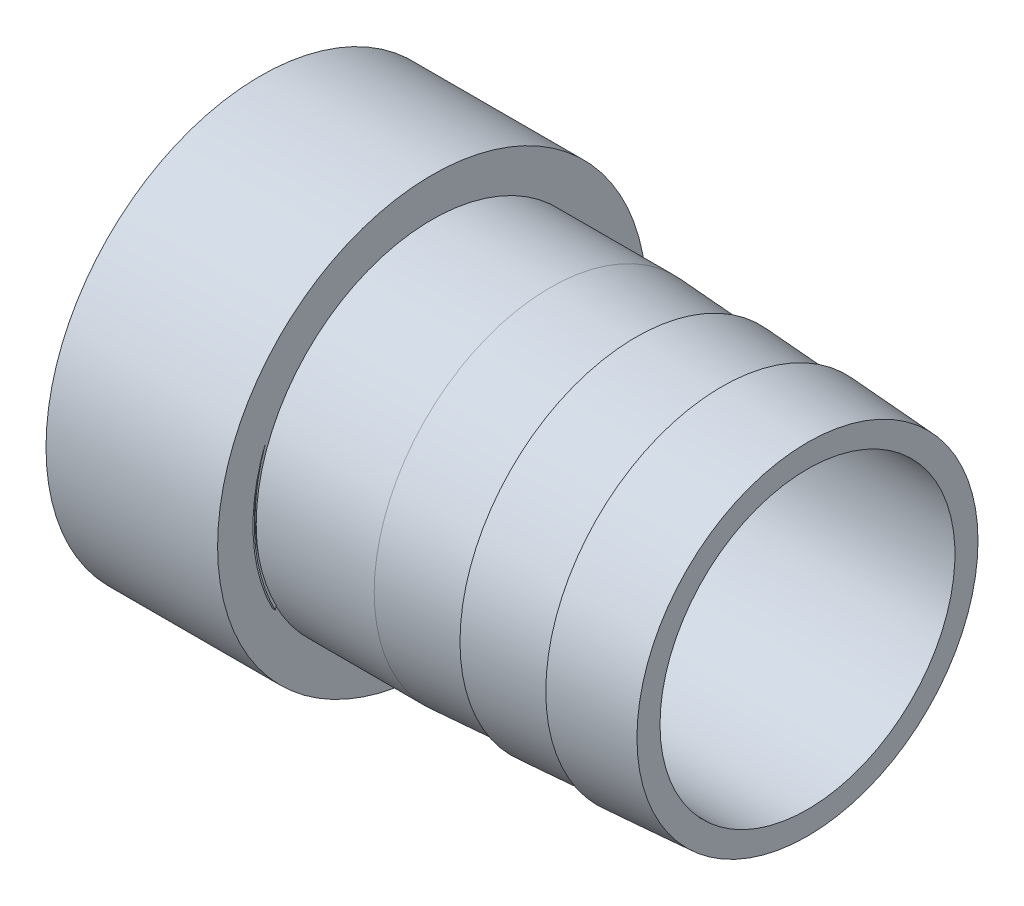
SolidWorks part; units mm, degrees
ref_plane "Płaszczyzna przednia" through (0, 0, 0) normal (0, 0, 1) x (1, 0, 0)
ref_plane "Płaszczyzna górna" through (0, 0, 0) normal (0, 1, 0) x (1, 0, 0)
ref_plane "Płaszczyzna prawa" through (0, 0, 0) normal (1, 0, 0) x (0, 0, -1)
sketch "Szkic1" plane through (0, 0, 0) normal (0, 0, 1) x (1, 0, 0)
  line L0 (0, 0) -> (21.6019, 0) construction
  line L1 (0, 16.4) -> (11, 16.4)
  line L2 (11, 16.4) -> (19, 15.9)
  line L3 (19, 15.9) -> (19, 16.4)
  line L4 (19, 16.4) -> (27, 15.9)
  line L5 (27, 15.9) -> (27, 16.4)
  line L6 (27, 16.4) -> (35, 15.9)
  line L7 (35, 15.9) -> (35, 13.75)
  line L8 (35, 15.9) -> (35, 16.4) [skipped]
  line L9 (35, 13.75) -> (-1.2, 13.75)
  line L10 (-1.2, 13.75) -> (-1.2, 16.7)
  line L11 (-1.2, 16.7) -> (-16, 16.7)
  line L12 (-16, 16.7) -> (-16, 20)
  line L13 (-16, 20) -> (0, 20)
  line L14 (0, 20) -> (0, 16.4)
  dimension "D1" = 11
  dimension "D2" = 16.4
  dimension "D3" = 8
  dimension "D4" = 15.9
  dimension "D6" = 13.75
  dimension "D7" = 14.8
  dimension "D8" = 20
  dimension "D9" = 3.3
  dimension "D10" = 51
  dimension "D5" = 3
revolve "Obrót1" add sketch "Szkic1" angle 360 about L0
thread "Gwint1" pitch 1.9538 method extrude profile "Profil gwintu1" start angle 0, offset 0, length 0, pitch 1.9538, diameter 33.4
ref_plane "Płaszczyzna1" through (-16, 0, -16.7) normal (0, 1, 0) x (0, 0, 1)
sketch "Profil gwintu1" plane through (-16, 0, -16.7) normal (0, 1, 0) x (0, 0, 1)
  line L0 (0, 0) -> (0, 1.9538) construction
  line L1 (0, 0) -> (1.0576, 0.6106)
  line L2 (1.0576, 0.6106) -> (1.0576, 0.8548)
  line L3 (1.0576, 0.8548) -> (0, 1.4654)
  line L4 (1.0576, 0.7327) -> (0, 0.7327) construction
  line L11 (0, 0) -> (0, 1.4654)
  point P2 (0, 0)
  dimension "Pitch" = 1.9538
  dimension "Profile_Angle" = 60
  dimension "Profile_Land" = 0.2442
  dimension "Profile_Height" = 1.0576
